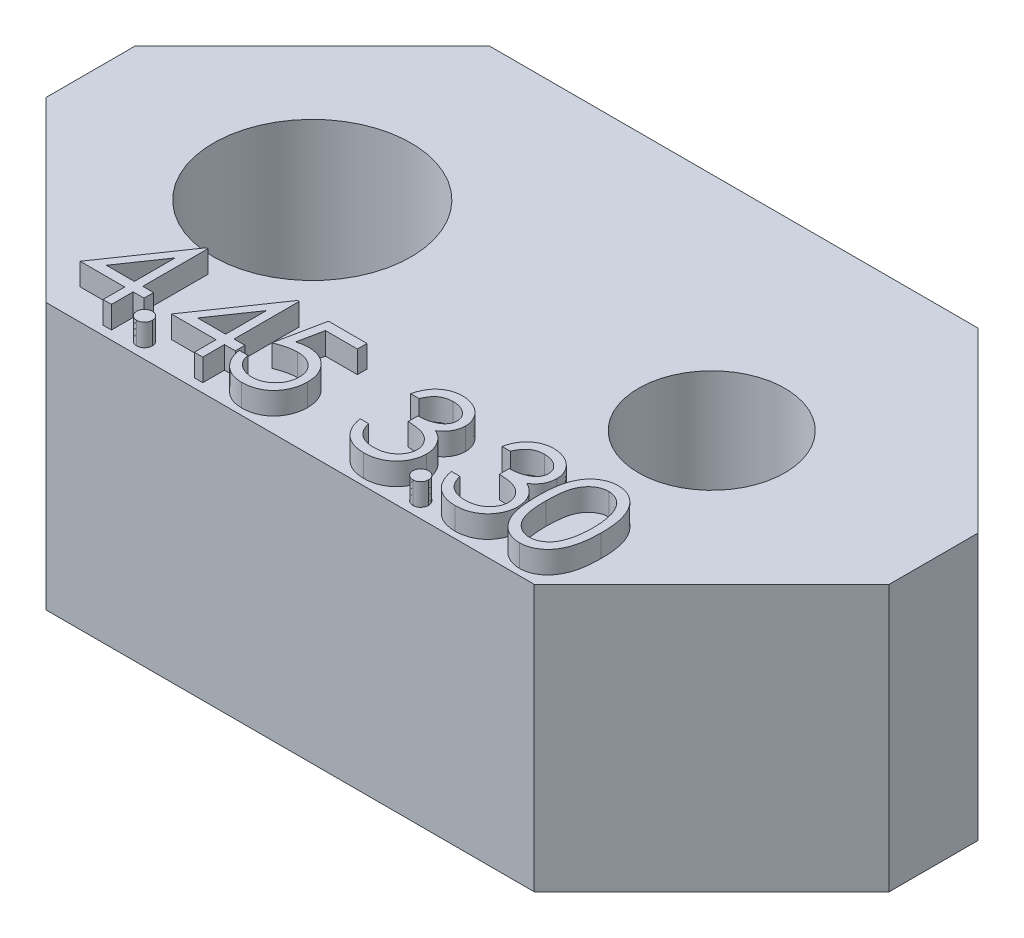
SolidWorks part; units mm, degrees
ref_plane "Спереди" through (0, 0, 0) normal (0, 0, 1) x (1, 0, 0)
ref_plane "Сверху" through (0, 0, 0) normal (0, 1, 0) x (1, 0, 0)
ref_plane "Справа" through (0, 0, 0) normal (1, 0, 0) x (0, 0, -1)
sketch "Эскиз1" plane through (0, 0, 0) normal (0, 1, 0) x (1, 0, 0)
  line L0 (-9.5, 0) -> (9.5, 0) construction
  line L1 (5.5, 5) -> (-5.5, 5)
  line L2 (9.5, 1) -> (9.5, -1)
  line L3 (5.5, -5) -> (-5.5, -5)
  line L4 (-9.5, 1) -> (-9.5, -1)
  line L5 (9.5, 5) -> (-9.5, -5) construction
  line L6 (9.5, -5) -> (-9.5, 5) construction
  line L7 (-5.5, 5) -> (-9.5, 1)
  line L8 (-9.5, -1) -> (-5.5, -5)
  line L9 (9.5, -1) -> (5.5, -5)
  line L10 (5.5, 5) -> (9.5, 1)
  circle A0 centre (-4.5, 0) radius 2.225
  circle A1 centre (4.5, 0) radius 1.65
  point P0 (0, 0)
  dimension "D1" = 4.45
  dimension "D2" = 3.3
  dimension "D3" = 5
  dimension "D4" = 9
  dimension "D5" = 5
  dimension "D6" = 10
  dimension "D7" = 19
extrude "Бобышка-Вытянуть1" add sketch "Эскиз1" along normal blind 6 contours L10 L1 L7 L4 L8 L3 L9 L2 A1 A0 region at (0.2353, 0, 0)
extrude "Бобышка-Вытянуть2" add sketch "Эскиз1<3>" along normal blind 2 contours A0 | A1 region at (-4.5, 0, 0) region at (4.5, 0, 0)
sketch "Эскиз1<3>" plane through (0, 0, 0) normal (0, 1, 0) x (1, 0, 0) same geometry as "Эскиз1"
sketch "Эскиз3" plane through (0, 6, 0) normal (0, 1, 0) x (1, 0, 0)
  line L0 (-5.5, -5) -> (-5.5, -4.8) construction
  line L1 (-5.5, -4.8) -> (5.5, -4.8) construction
  text T0 "4.45  3.30" font "Century Gothic" height in points 8
  dimension "D1" = 0.2
  dimension "D2" = 11
extrude "Бобышка-Вытянуть3" add sketch "Эскиз3" along normal blind 0.5
